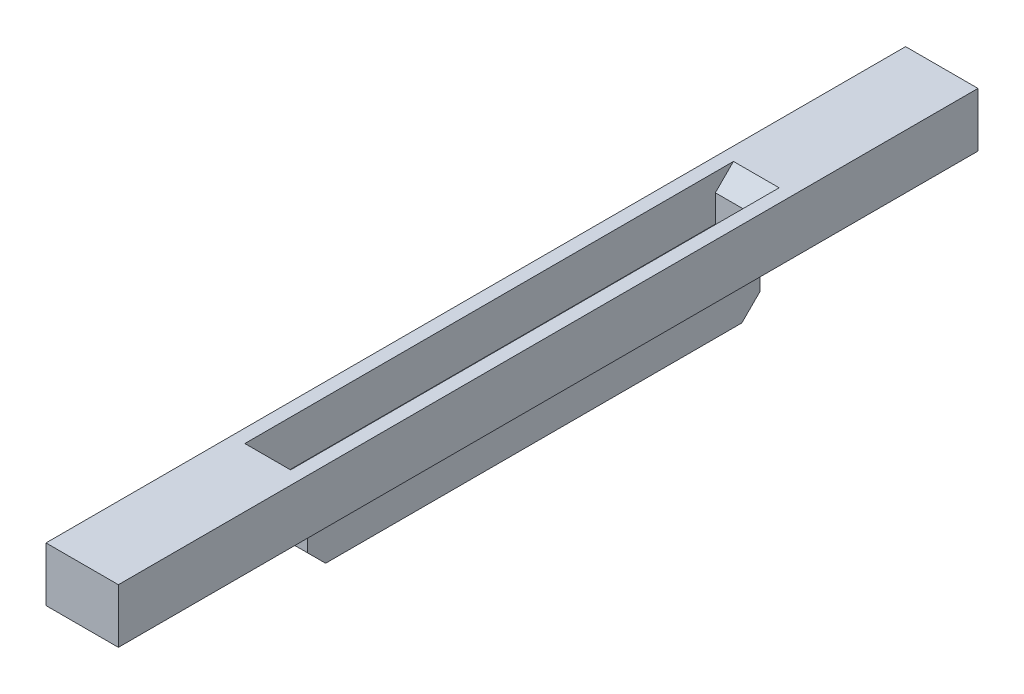
SolidWorks part; units mm, degrees
ref_plane "Front Plane" through (0, 0, 0) normal (0, 0, 1) x (1, 0, 0)
ref_plane "Top Plane" through (0, 0, 0) normal (0, 1, 0) x (1, 0, 0)
ref_plane "Right Plane" through (0, 0, 0) normal (1, 0, 0) x (0, 0, -1)
sketch "Sketch1" plane through (0, 0, 0) normal (0, 1, 0) x (1, 0, 0)
  line L1 (-4, 47.5) -> (4, 47.5)
  line L2 (-4, 47.5) -> (-4, -47.5)
  line L3 (-4, -47.5) -> (4, -47.5)
  line L4 (4, 47.5) -> (4, -47.5)
  line L5 (-4, 47.5) -> (4, -47.5) construction
  line L6 (-4, -47.5) -> (4, 47.5) construction
  line L7 (-2.525, 25) -> (2.525, 25)
  line L8 (-2.525, 25) -> (-2.525, -25)
  line L9 (-2.525, -25) -> (2.525, -25)
  line L10 (2.525, 25) -> (2.525, -25)
  line L11 (-2.525, 25) -> (2.525, -25) construction
  line L12 (-2.525, -25) -> (2.525, 25) construction
  point P0 (0, 0)
  point P5 (0, 0)
  dimension "D1" = 8
  dimension "D2" = 95
  dimension "D3" = 50
  dimension "D4" = 5.05
extrude "Boss-Extrude1" add sketch "Sketch1" along normal blind 5
extrude "Boss-Extrude2" add sketch "Sketch1<2>" against normal blind 1 contours L4 L1 L2 L3 L7 L10 L9 L8 | L10 L7 L8 L9 region at (0, 0, -46.5466) region at (0, 0, 0)
sketch "Sketch1<2>" plane through (0, 0, 0) normal (0, 1, 0) x (1, 0, 0) same geometry as "Sketch1"
sketch "Sketch2" plane through (0, -1, 0) normal (0, -1, 0) x (1, 0, 0)
  line L1 (2.4, 25) -> (-2.4, 25)
  line L2 (2.4, 25) -> (2.4, -25)
  line L3 (2.4, -25) -> (-2.4, -25)
  line L4 (-2.4, 25) -> (-2.4, -25)
  line L5 (2.4, 25) -> (-2.4, -25) construction
  line L6 (2.4, -25) -> (-2.4, 25) construction
  point P0 (0, 0)
  dimension "D1" = 4.8
  dimension "D2" = 50
extrude "Boss-Extrude3" add sketch "Sketch2" along normal blind 5
chamfer "Chamfer2" distance 2 angle 45 4 edges at (0, -6, -25) (0, -6, 25) (0, 5, -25) (0, 5, 25)
